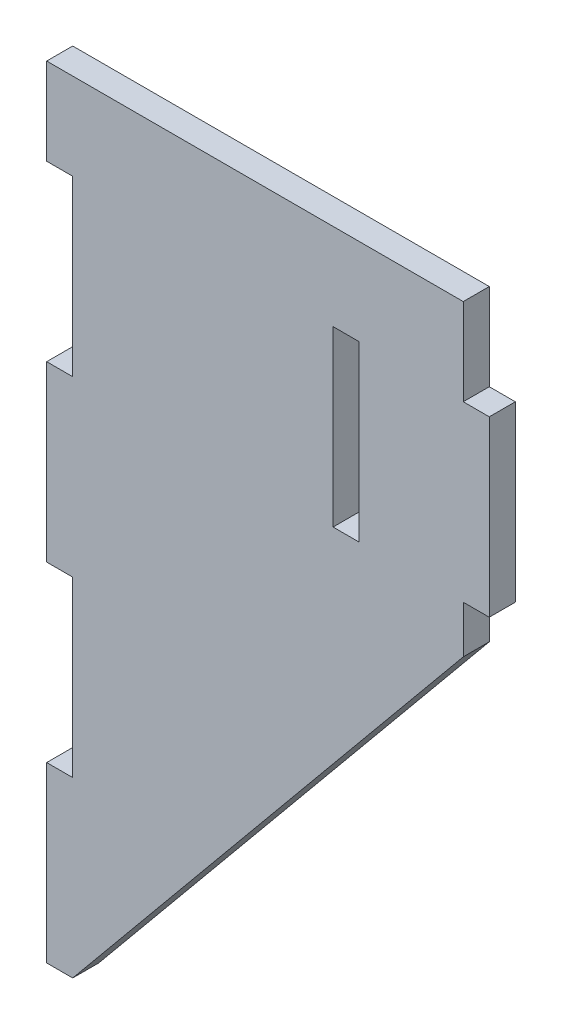
SolidWorks part; units mm, degrees
material "Acrilico TEC"
ref_plane "Front Plane" through (0, 0, 0) normal (0, 0, 1) x (1, 0, 0)
ref_plane "Top Plane" through (0, 0, 0) normal (0, 1, 0) x (1, 0, 0)
ref_plane "Right Plane" through (0, 0, 0) normal (1, 0, 0) x (0, 0, -1)
sketch "Sketch1" plane through (0, 0, 0) normal (0, 0, 1) x (1, 0, 0)
  line L0 (-3, 60) -> (-3, 40)
  line L1 (-3, 40) -> (0, 40)
  line L2 (0, 40) -> (0, 20)
  line L3 (0, 20) -> (-3, 20)
  line L4 (-3, 20) -> (-3, 0)
  line L5 (-3, 60) -> (0, 60)
  line L6 (0, 60) -> (0, 80)
  line L7 (0, 80) -> (-3, 80)
  line L8 (-3, 80) -> (-3, 90)
  line L9 (-3, 90) -> (15, 90)
  line L10 (15, 90) -> (15, 75) construction
  line L11 (-3, 0) -> (0, 0)
  line L12 (15, 90) -> (45, 90)
  line L14 (30, 80) -> (33, 80)
  line L15 (30, 60) -> (30, 80)
  line L16 (33, 60) -> (30, 60)
  line L17 (45, 90) -> (45, 80)
  line L18 (45, 80) -> (48, 80)
  line L19 (48, 80) -> (48, 60)
  line L20 (48, 60) -> (45, 60)
  line L22 (0, 0) -> (45, 54.5455)
  line L23 (45, 60) -> (45, 54.5455)
  line L25 (33, 60) -> (33, 80)
  dimension "D1" = 10
  dimension "D2" = 20
  dimension "D3" = 20
  dimension "D4" = 20
  dimension "D5" = 20
  dimension "D6" = 3
  dimension "D7" = 3
  dimension "D8" = 15
  dimension "D9" = 15
  dimension "D10" = 30
  dimension "D11" = 3
  dimension "D12" = 20
  dimension "D13" = 5.4545
extrude "Boss-Extrude1" add sketch "Sketch1" along normal blind 3
